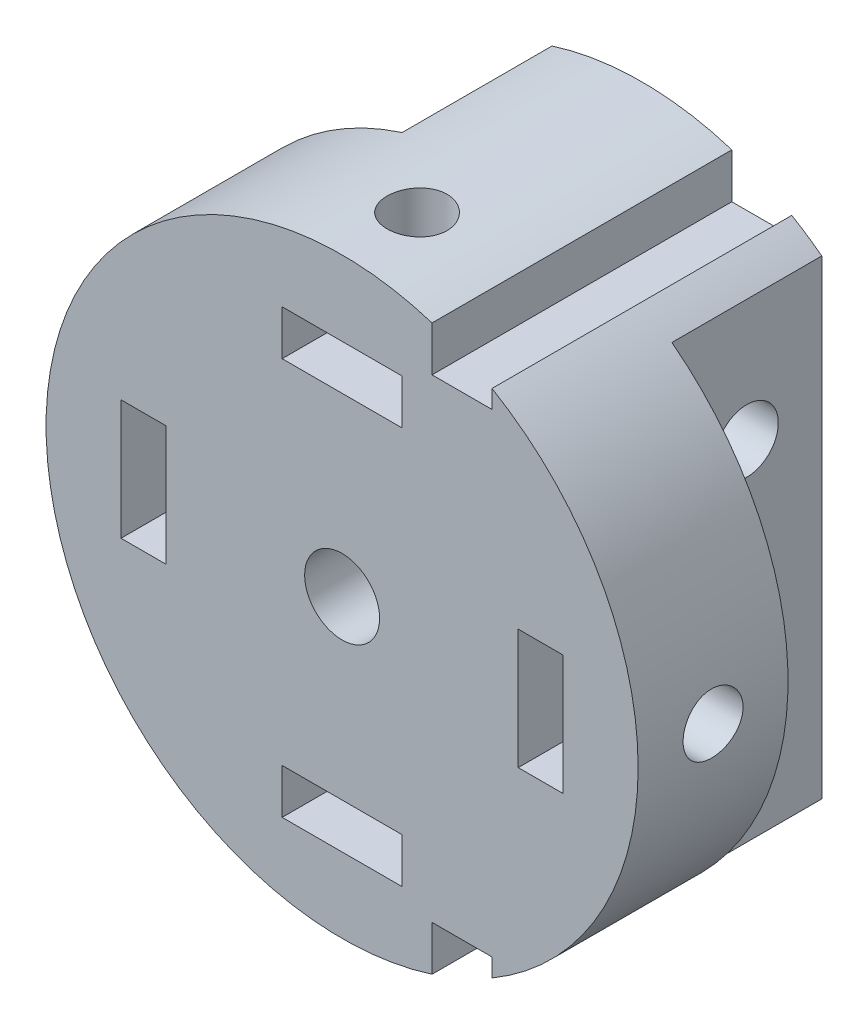
SolidWorks part; units mm, degrees
ref_plane "Front Plane" through (0, 0, 0) normal (1, 0, 0) x (0, 1, 0)
ref_plane "Top Plane" through (0, 0, 0) normal (0, 0, 1) x (0, 1, 0)
ref_plane "Right Plane" through (0, 0, 0) normal (0, 1, 0) x (-1, 0, 0)
sketch "Sketch3" plane through (0, 0, 0) normal (0, 0, 1) x (0, 1, 0)
  line L0 (0, 0) -> (25.0825, 0) construction
  circle A0 centre (0, 0) radius 25.0825
  circle A1 centre (0, 0) radius 3.175
  dimension "D1" = 50.165
  dimension "D2" = 6.35
extrude "base" add sketch "Sketch3" along normal blind 12.7
ref_plane "Plane1" through (-25.0825, 0, 0) normal (-1, 0, 0) x (0, 0, 1)
sketch "Sketch6" plane through (0, 0, 0) normal (0, 0, -1) x (1, 0, 0)
  line L0 (0, 0) -> (15.24, 0) construction
  line L1 (15.24, 19.9217) -> (-7.62, 19.9217) construction
  line L2 (15.24, 19.9217) -> (15.24, -19.9217)
  line L3 (15.24, -19.9217) -> (-7.62, -19.9217) construction
  line L5 (-7.62, 23.897) -> (-7.62, -23.897)
  circle A0 centre (0, 0) radius 25.0825 construction
  arc A1 (-7.62, 23.897) -> (15.24, 19.9217) centre (0, 0) cw
  arc A2 (-7.62, -23.897) -> (15.24, -19.9217) centre (0, 0) ccw
  circle A3 centre (0, 0) radius 3.175
  circle A4 centre (0, 0) radius 3.175 construction
  dimension "D1" = 22.86
  dimension "D2" = 15.24
extrude "upper_bolts_connection" add sketch "Sketch6" along normal blind 12.7
sketch "Sketch8" plane through (0, 0, -12.7) normal (0, 0, -1) x (1, 0, 0)
  line L1 (6.5991, 0) -> (3.2996, 5.715)
  line L2 (3.2996, 5.715) -> (-3.2996, 5.715)
  line L3 (-3.2996, 5.715) -> (-6.5991, 0)
  line L4 (-6.5991, 0) -> (-3.2996, -5.715)
  line L5 (-3.2996, -5.715) -> (3.2996, -5.715)
  line L6 (3.2996, -5.715) -> (6.5991, 0)
  circle A0 centre (0, 0) radius 5.715 construction
  dimension "D1" = 11.43
extrude "nut_hole" cut sketch "Sketch8" against normal blind 8.89
sketch "Sketch9" plane through (-7.62, 0, 0) normal (-1, 0, 0) x (0, 0, 1)
  circle A0 centre (-6.35, -9.525) radius 2.667
  circle A1 centre (-6.35, 9.525) radius 2.667
  circle A2 centre (-6.35, 9.525) radius 2.667 construction
  circle A3 centre (-6.35, -9.525) radius 2.667 construction
extrude "upper_boltholes" cut sketch "Sketch9" against normal up to next
sketch "Sketch13" plane through (-25.0825, 0, 0) normal (-1, 0, 0) x (0, 0, 1)
  line L0 (0, 0) -> (12.7, 0) construction
  line L1 (12.2159, 0) -> (9.2829, 5.08) construction
  line L2 (9.2829, 5.08) -> (3.4171, 5.08) construction
  line L3 (3.4171, 5.08) -> (0.4841, 0)
  line L4 (0.4841, 0) -> (3.4171, -5.08)
  line L5 (3.4171, -5.08) -> (9.2829, -5.08) construction
  line L6 (9.2829, -5.08) -> (12.2159, 0) construction
  line L7 (12.7, -25.0825) -> (12.7, 25.0825) construction
  line L8 (3.4171, 5.08) -> (12.7, 5.08)
  line L9 (12.7, 5.08) -> (12.7, -5.08)
  line L10 (12.7, -5.08) -> (3.4171, -5.08)
  circle A0 centre (6.35, 0) radius 5.08 construction
  dimension "D1" = 10.16
extrude "nut_recess" cut sketch "Sketch13" against normal blind 3.81 from offset 6.35 offset against normal yes
sketch "Sketch14" plane through (-25.0825, 0, 0) normal (-1, 0, 0) x (0, 0, 1)
  line L0 (0, 0) -> (12.7, 0) construction
  line L1 (12.7, -25.0825) -> (12.7, 25.0825) construction
  circle A0 centre (6.35, 0) radius 2.54
  dimension "D1" = 5.08
extrude "radial_bolt_hole" cut sketch "Sketch14" against normal blind 15.24
pattern_circular "CirPattern2" count 4 over 360 about axis through (0, 0, 12.7) along (0, 0, -1) of "radial_bolt_hole", "nut_recess" reverse direction yes
sketch "Sketch15" plane through (0, 0, -12.7) normal (0, 0, -1) x (1, 0, 0)
  line L0 (15.24, -19.9217) -> (15.24, 19.9217) construction
  line L1 (7.62, 23.897) -> (12.7, 23.897)
  line L2 (7.62, 23.897) -> (7.62, 20.087)
  line L3 (7.62, 20.087) -> (12.7, 20.087)
  line L5 (12.7, 20.087) -> (12.7, 23.897)
  arc A0 (15.24, 19.9217) -> (-7.62, 23.897) centre (0, 0) ccw construction
  point P9 (12.7, 21.6297)
  dimension "D1" = 2.54
  dimension "D2" = 5.08
  dimension "D3" = 3.81
  dimension "D4" = 1.5426
extrude "wire_passthrough" cut sketch "Sketch15" against normal up to next
mirror "wire_passthrough_mirror" about plane through (0, 0, 0) normal (0, 1, 0) of "wire_passthrough"
